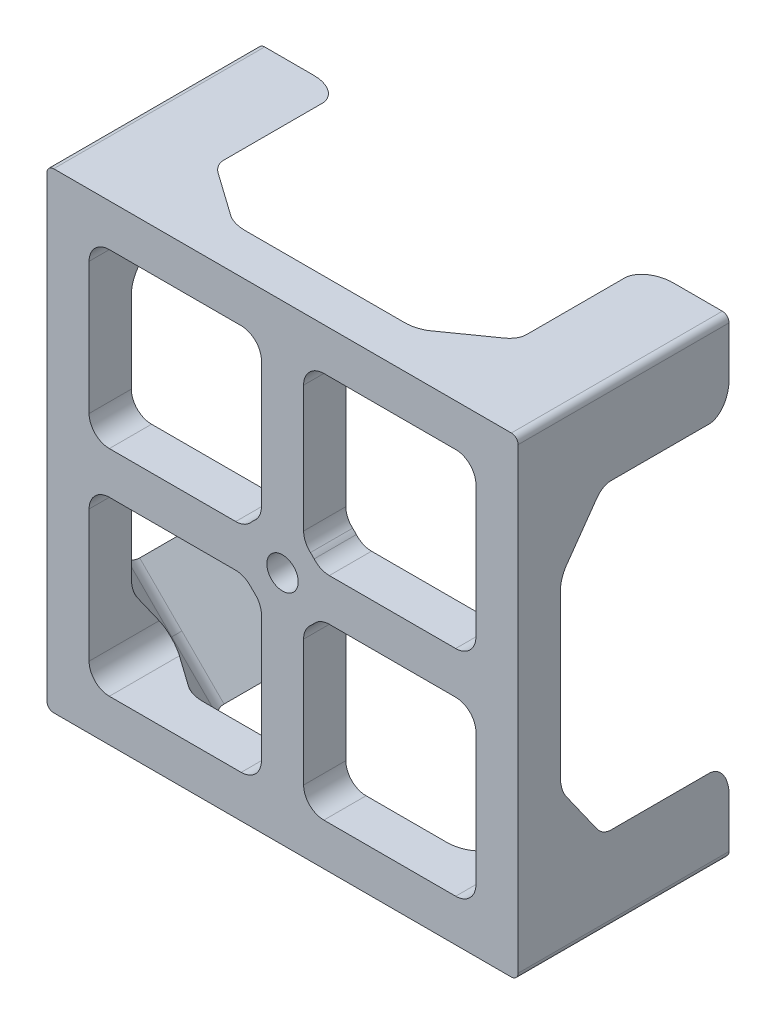
SolidWorks part; units mm, degrees
ref_plane "Front Plane" through (0, 0, 0) normal (0, 0, 1) x (1, 0, 0)
ref_plane "Top Plane" through (0, 0, 0) normal (0, 1, 0) x (1, 0, 0)
ref_plane "Right Plane" through (0, 0, 0) normal (1, 0, 0) x (0, 0, -1)
sketch "Sketch1" plane through (0, 0, 0) normal (0, 0, 1) x (1, 0, 0)
  line L0 (-97.6376, 73.8886) -> (-94.4626, 73.8886)
  line L1 (-79.9084, 73.8886) -> (-97.6376, 73.8886) construction
  line L2 (-94.4626, 73.8886) -> (-97.6376, 70.7136)
  line L3 (-97.6376, 73.8886) -> (-97.6376, 56.1594) construction
  line L4 (-97.6376, 70.7136) -> (-97.6376, 73.8886)
  line L5 (-88.773, 73.8886) -> (-88.773, 56.1594) construction
  line L6 (-97.6376, 56.1594) -> (-79.9084, 56.1594) construction
  line L7 (-88.773, 65.024) -> (-79.9084, 65.024) construction
  line L8 (-79.9084, 56.1594) -> (-79.9084, 73.8886) construction
  line L9 (-79.9084, 70.7136) -> (-79.9084, 73.8886)
  line L10 (-83.0834, 73.8886) -> (-79.9084, 70.7136)
  line L11 (-79.9084, 73.8886) -> (-83.0834, 73.8886)
  line L12 (-79.9084, 56.1594) -> (-83.0834, 56.1594)
  line L13 (-83.0834, 56.1594) -> (-79.9084, 59.3344)
  line L14 (-79.9084, 59.3344) -> (-79.9084, 56.1594)
  line L15 (-97.6376, 59.3344) -> (-97.6376, 56.1594)
  line L16 (-94.4626, 56.1594) -> (-97.6376, 59.3344)
  line L17 (-97.6376, 56.1594) -> (-94.4626, 56.1594)
  dimension "D1" = 3.175
extrude "Boss-Extrude1" add sketch "Sketch1" along normal blind 6.35
sketch "Sketch2" plane through (0, 0, 6.35) normal (0, 0, 1) x (1, 0, 0)
  line L0 (-88.773, 73.8886) -> (-88.773, 56.1594)
  line L1 (-97.6376, 73.8886) -> (-79.9084, 73.8886)
  line L2 (-97.6376, 73.8886) -> (-97.6376, 56.1594)
  line L3 (-97.6376, 56.1594) -> (-79.9084, 56.1594)
  line L4 (-79.9084, 73.8886) -> (-79.9084, 56.1594)
  line L5 (-97.6376, 73.8886) -> (-79.9084, 56.1594) construction
  line L6 (-97.6376, 56.1594) -> (-79.9084, 73.8886) construction
  line L7 (-97.6376, 65.024) -> (-79.9084, 65.024)
  point P4 (-88.773, 65.024)
extrude "Extrude-Thin1" add sketch "Sketch2" along normal blind 1.5875 separate body thin contours L0 | L7 thin type mid plane wall 1.5875
extrude "Extrude-Thin2" add sketch "Sketch2<3>" along normal blind 1.5875 thin contours L2 L3 L4 L1 thin type one direction reverse wall 1.5875
sketch "Sketch2<3>" plane through (0, 0, 6.35) normal (0, 0, 1) x (1, 0, 0) same geometry as "Sketch2"
sketch "Sketch6" plane through (0, 0, 7.9375) normal (0, 0, 1) x (1, 0, 0)
  line L0 (-89.5668, 65.8177) -> (-87.9793, 64.2302) construction
  circle A0 centre (-88.773, 65.024) radius 1.5875
  dimension "D1" = 3.175
extrude "Boss-Extrude3" add sketch "Sketch6" against normal up to surface (1.5875 mm away) up to face at (-89.0329, 65.1705, 6.35)
hole_wizard "#56 (0.0465) Diameter Hole1" positions "Sketch5" profile "Sketch4" hole size "#56" standard "ANSI Inch" end condition through all
sketch "Sketch5" plane through (0, 0, 7.9375) normal (0, 0, 1) x (1, 0, 0)
  point P6 (-88.773, 65.024)
sketch "Sketch4" plane through (-88.773, 65.024, 7.9375) normal (1, 0, 0) x (0, -1, 0)
  line L0 (0, 0) -> (0, 7.9375)
  line L1 (0, 7.9375) -> (0.5905, 7.9375)
  line L2 (0.5905, 7.9375) -> (0.5905, 0)
  line L5 (0.5905, 0) -> (0, 0)
  line L11 (0, -6.35) -> (0, 107.95) construction
  dimension "Thru Hole Dia." = 1.1811
  dimension "Thru Hole Depth" = 7.9375
chamfer "Chamfer1" distance 1.5875 angle 45 8 edges at (-82.2897, 56.9531, 6.35) (-80.7022, 58.5406, 6.35) (-80.7022, 71.5073, 6.35) (-82.2897, 73.0948, 6.35) (-95.2564, 56.9531, 6.35) (-96.8439, 58.5406, 6.35)
fillet "Fillet2" radius 0.762 20 edges at (-89.5668, 72.3011, 7.1437) (-96.0501, 72.3011, 6.35) (-96.0501, 65.8177, 7.1437) (-90.1478, 65.8177, 7.1437) (-89.5668, 66.3988, 7.1437) (-96.0501, 64.2302, 7.1437) (-96.0501, 57.7469, 6.35) (-89.5668, 57.7469, 7.1437) (-89.5668, 63.6492, 7.1437) (-87.9793, 63.6492, 7.1437) (-87.9793, 57.7469, 7.1437) (-81.4959, 57.7469, 6.35) (-81.4959, 64.2302, 7.1437) (-87.3982, 64.2302, 7.1437) (-87.3982, 65.8177, 7.1437) (-81.4959, 65.8177, 7.1437) (-81.4959, 72.3011, 6.35) (-87.9793, 72.3011, 7.1437) (-87.9793, 66.3988, 7.1437) (-90.1478, 64.2302, 7.1437)
fillet "Fillet3" radius 0.762 20 edges at (-96.8439, 58.5406, 4.7625) (-82.2897, 56.9531, 4.7625) (-80.7022, 71.5073, 4.7625) (-96.8439, 71.5073, 4.7625) (-96.0501, 72.3011, 0) (-81.4959, 72.3011, 0) (-81.4959, 57.7469, 0) (-96.0501, 57.7469, 0) (-95.2564, 56.9531, 4.7625) (-80.7022, 58.5406, 4.7625) (-82.2897, 73.0948, 4.7625) (-96.8439, 60.7857, 6.35) (-93.0113, 56.9531, 6.35) (-84.5347, 73.0948, 6.35) (-80.7022, 69.2623, 6.35) (-80.7022, 60.7857, 6.35) (-84.5347, 56.9531, 6.35) (-93.0113, 73.0948, 6.35) (-96.8439, 69.2623, 6.35) (-95.2564, 73.0948, 4.7625)
fillet "Fillet4" radius 0.254 4 edges at (-79.9084, 56.1594, 3.9688) (-79.9084, 73.8886, 3.9688) (-97.6376, 73.8886, 3.9688) (-97.6376, 56.1594, 3.9688)
